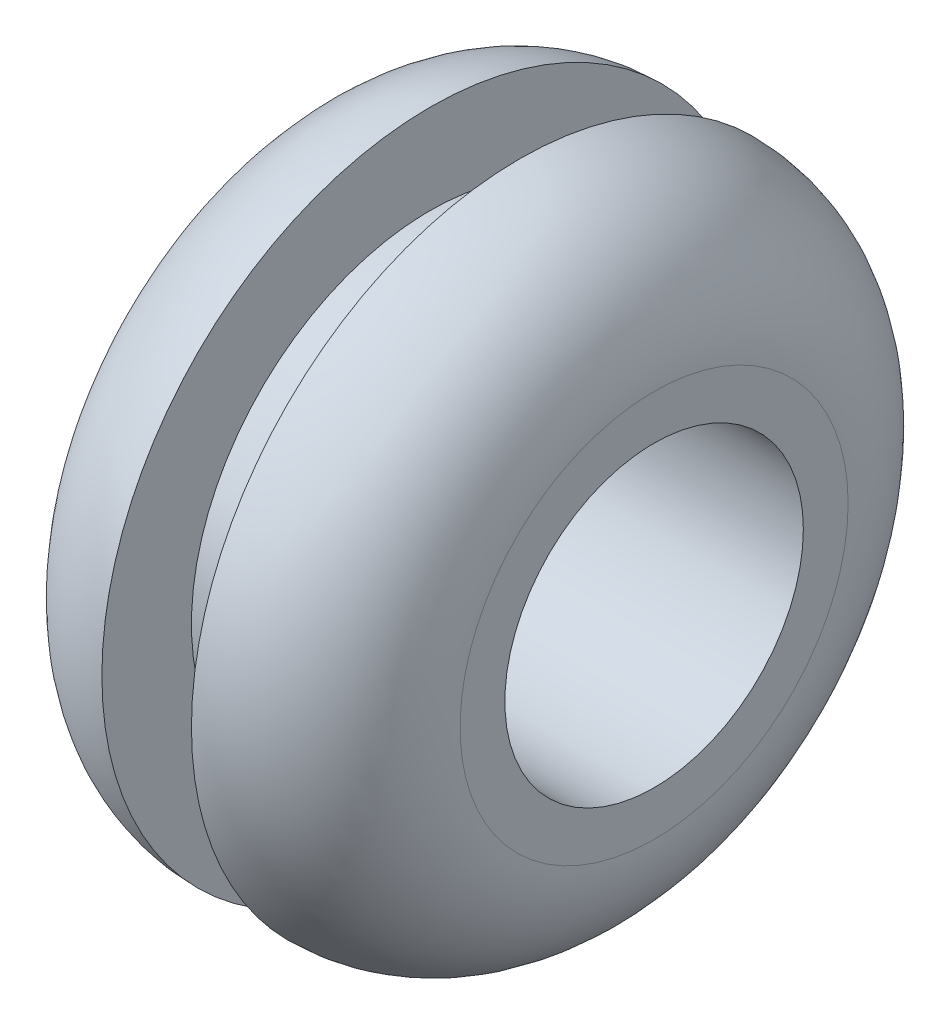
SolidWorks part; units mm, degrees
ref_plane "Plan de face" through (0, 0, 0) normal (0, 0, 1) x (1, 0, 0)
ref_plane "Plan de dessus" through (0, 0, 0) normal (0, 1, 0) x (1, 0, 0)
ref_plane "Plan de droite" through (0, 0, 0) normal (1, 0, 0) x (0, 0, -1)
sketch "Esquisse1" plane through (0, 0, 0) normal (0, 0, 1) x (1, 0, 0)
  line L0 (-27.9934, 2.5) -> (-21.9934, 2.5)
  line L1 (-21.9934, 2.5) -> (-21.9934, 5.5)
  line L2 (-21.9934, 5.5) -> (-24.2434, 5.5)
  line L3 (-24.2434, 5.5) -> (-24.2434, 4)
  line L4 (-24.2434, 4) -> (-25.7434, 4)
  line L5 (-25.7434, 4) -> (-25.7434, 5.5)
  line L6 (-25.7434, 5.5) -> (-27.9934, 5.5)
  line L7 (-27.9934, 5.5) -> (-27.9934, 2.5)
  line L8 (24.6068, 0) -> (-60.0317, 0) construction
  dimension "D1" = 6
  dimension "D2" = 1.5
  dimension "D3" = 2.25
  dimension "D4" = 2.5
  dimension "D5" = 5.5
  dimension "D6" = 5.5
  dimension "D7" = 1.5
revolve "Révolution1" add sketch "Esquisse1" angle 360 about L8
fillet "Congé1" radius 2.25 2 edges at (-21.9934, 0, -5.5) (-27.9934, 0, -5.5)
